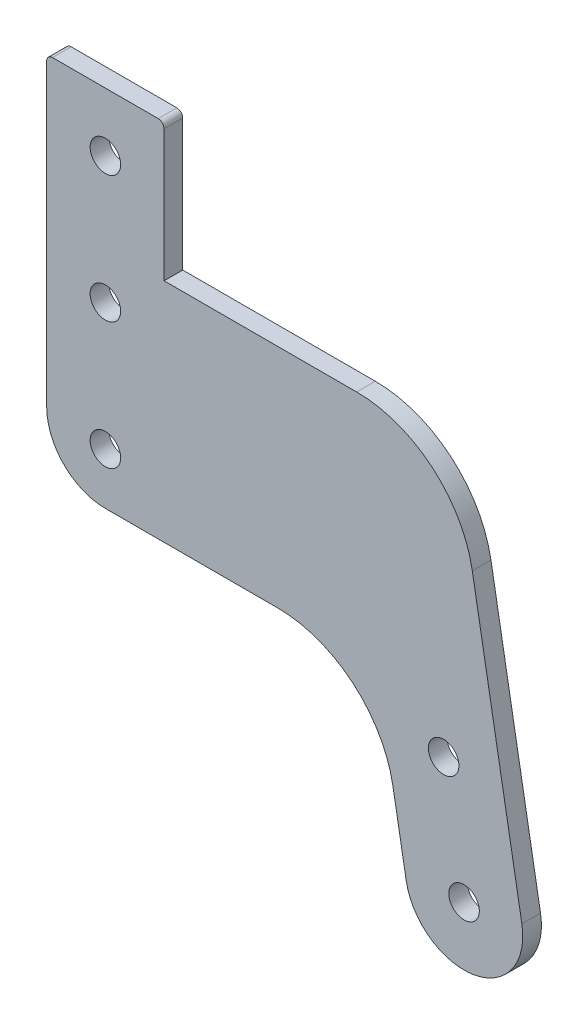
SolidWorks part; units mm, degrees
ref_plane "Front Plane" through (0, 0, 0) normal (0, 0, 1) x (1, 0, 0)
ref_plane "Top Plane" through (0, 0, 0) normal (0, 1, 0) x (1, 0, 0)
ref_plane "Right Plane" through (0, 0, 0) normal (1, 0, 0) x (0, 0, -1)
ref_plane "Plane1" through (0, 0, 423.175) normal (0, 0, 1) x (1, 0, 0)
sketch "Sketch11" plane through (0, 0, 423.175) normal (0, 0, 1) x (1, 0, 0)
  line L0 (80.9329, 272.1931) -> (72.4922, 320.0489)
  line L1 (52.7962, 336.575) -> (20, 336.575)
  line L2 (20, 336.575) -> (20, 359)
  line L3 (19, 360) -> (1, 360)
  line L4 (0, 359) -> (0, 308)
  line L5 (10, 298) -> (39.289, 298)
  line L6 (58.9847, 281.4758) -> (61.2361, 268.7181)
  arc A0 (61.2361, 268.7181) -> (72.8209, 260.608) centre (71.0839, 270.456) ccw
  arc A1 (72.8218, 260.6081) -> (80.9329, 272.1931) centre (71.0849, 270.4561) ccw
  arc A2 (72.4922, 320.0489) -> (52.7962, 336.575) centre (52.7962, 316.575) ccw
  arc A3 (20, 359) -> (19, 360) centre (19, 359) ccw
  arc A4 (1, 360) -> (0, 359) centre (1, 359) ccw
  arc A5 (0, 308) -> (10, 298) centre (10, 308) ccw
  arc A6 (39.289, 298) -> (58.9847, 281.4758) centre (39.289, 278) cw
  spline S0 degree 3 poles (72.8209, 260.608) (72.8212, 260.608) (72.8215, 260.6081) (72.8218, 260.6081) knots 0 0 0 0 1 1 1 1
base flange "Base-Flange1" sketch "Sketch11" thickness 3.175 reverse thickness direction yes parameters "D1"=0
hole_wizard "Ø5.2 (5.2) Diameter Hole1" positions "Sketch17" profile "Sketch16" hole size "Ø5.2" standard "ANSI Metric"
sketch "Sketch17" plane through (0, 0, 423.175) normal (0, 0, 1) x (1, 0, 0)
  point P0 (67.611, 290.1521)
  point P1 (10, 350)
  point P2 (10, 328.3784)
  point P3 (10, 306.7568)
  point P4 (71.0839, 270.456)
sketch "Sketch16" plane through (67.611, 290.1521, 423.175) normal (1, 0, 0) x (0, -1, 0)
  line L0 (0, 0) -> (0, 3.175)
  line L1 (0, 3.175) -> (2.6, 3.175)
  line L2 (2.6, 3.175) -> (2.6, 0)
  line L5 (2.6, 0) -> (0, 0)
  line L11 (0, -6.35) -> (0, 107.95) construction
  dimension "Thru Hole Dia." = 5.2
  dimension "Thru Hole Depth" = 3.175
sketch "Bend-Lines4" plane through (0, 0, 0) normal (0, 1, 0) x (1, 0, 0)
sketch "Bounding-Box4" plane through (0, 0, 0) normal (0, 1, 0) x (1, 0, 0)
sheet metal parameters "Sheet-Metal(5)" thickness 3.175 parameters "D1"=0
flat pattern "Flat-Pattern(5)" [suppressed]
sketch "Bend-Lines5" plane through (0, 0, 0) normal (0, 1, 0) x (1, 0, 0)
sketch "Bounding-Box5" [suppressed] plane through (0, 0, 0) normal (0, 1, 0) x (1, 0, 0)
sheet metal parameters "Sheet-Metal(6)" thickness 3.175 parameters "D1"=0
flat pattern "Flat-Pattern(5)"
sketch "Bend-Lines5" plane through (0, 0, 0) normal (0, 1, 0) x (1, 0, 0)
sketch "Bounding-Box5" [suppressed] plane through (0, 0, 0) normal (0, 1, 0) x (1, 0, 0)
